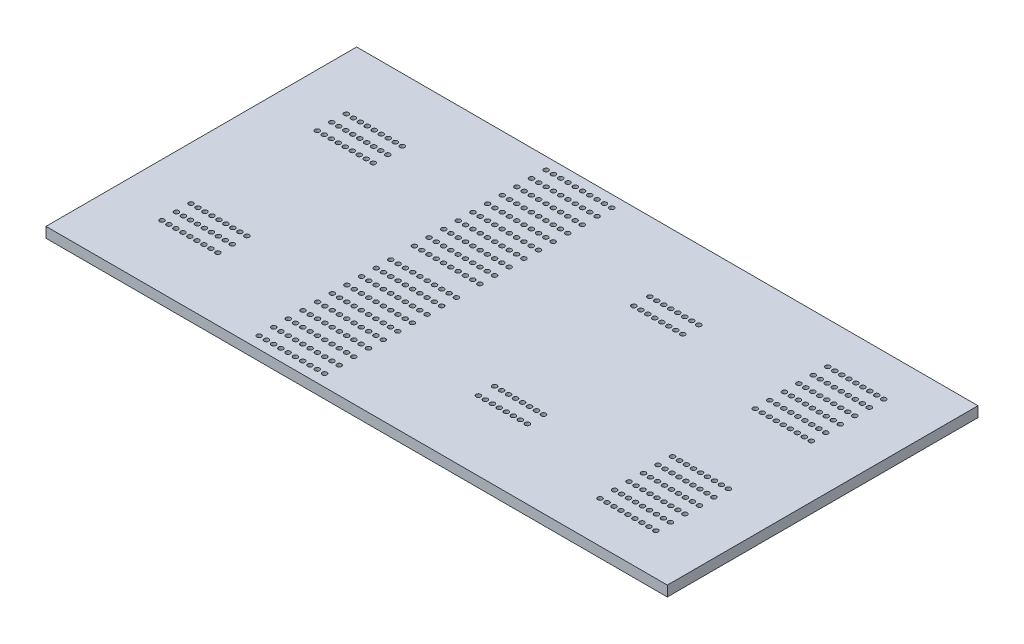
SolidWorks part; units mm, degrees
ref_plane "Plan de face" through (0, 0, 0) normal (0, 0, 1) x (1, 0, 0)
ref_plane "Plan de dessus" through (0, 0, 0) normal (0, 1, 0) x (1, 0, 0)
ref_plane "Plan de droite" through (0, 0, 0) normal (1, 0, 0) x (0, 0, -1)
sketch "Esquisse2" plane through (0, 0, 0) normal (0, 1, 0) x (1, 0, 0)
  line L1 (-60, -15) -> (60, -15)
  line L2 (-60, -15) -> (-60, 15)
  line L3 (-60, 15) -> (60, 15)
  line L4 (60, -15) -> (60, 15)
  line L5 (-60, -15) -> (60, 15) construction
  line L6 (-60, 15) -> (60, -15) construction
  point P0 (0, 0)
  dimension "D1" = 30
  dimension "D2" = 120
extrude "Boss.-Extru.1" add sketch "Esquisse2" along normal blind 2 contours L3 L4 L1 L2
sketch "Cavités" plane through (0, 0, 0) normal (0, 1, 0) x (1, 0, 0)
  line L0 (-60, -15) -> (60, -15) construction
  line L1 (-58.4, 15) -> (-30.4, 15) construction
  line L2 (-58.4, 15) -> (-58.4, -15) construction
  line L3 (-58.4, -15) -> (-30.4, -15) construction
  line L4 (-30.4, 15) -> (-30.4, -15) construction
  line L5 (-60, 15) -> (60, 15) construction
  line L6 (-28.8, 15) -> (-0.8, 15) construction
  line L7 (-28.8, 15) -> (-28.8, -15) construction
  line L8 (-28.8, -15) -> (-0.8, -15) construction
  line L9 (-0.8, 15) -> (-0.8, -15) construction
  line L10 (-30.4, 15) -> (-28.8, 15) construction
  line L11 (0.8, 15) -> (28.8, 15) construction
  line L12 (0.8, 15) -> (0.8, -15) construction
  line L13 (0.8, -15) -> (28.8, -15) construction
  line L14 (28.8, 15) -> (28.8, -15) construction
  line L15 (30.4, 15) -> (58.4, 15) construction
  line L16 (30.4, 15) -> (30.4, -15) construction
  line L17 (30.4, -15) -> (58.4, -15) construction
  line L18 (58.4, 15) -> (58.4, -15) construction
  line L19 (-0.8, 15) -> (0.8, 15) construction
  line L20 (28.8, 15) -> (30.4, 15) construction
  line L21 (-60, 15) -> (-58.4, 15) construction
  line L22 (58.4, 15) -> (60, 15) construction
  dimension "D1" = 28
  dimension "D2" = 1.6
sketch "Esquisse7" plane through (0, 2, 0) normal (0, 1, 0) x (1, 0, 0)
  line L0 (-58.4, 0) -> (-49.8, 0) construction
  line L1 (-49.8, 2.8) -> (-39, 2.8) construction
  line L2 (-49.8, 2.8) -> (-49.8, -2.8) construction
  line L3 (-49.8, -2.8) -> (-39, -2.8) construction
  line L4 (-39, 2.8) -> (-39, -2.8) construction
  line L5 (-58.4, 15) -> (-58.4, -15) construction
  line L6 (-39, 0) -> (-30.4, 0) construction
  line L7 (-30.4, 15) -> (-30.4, -15) construction
  dimension "D1" = 10.8
  dimension "D2" = 5.6
sketch "Esquisse8" plane through (0, 2, 0) normal (0, 1, 0) x (1, 0, 0)
  circle A0 centre (-49.8, 2.8) radius 0.45
  dimension "D1" = 0.9
extrude "Enlèv. mat.-Extru.3" cut sketch "Esquisse8" against normal up to next
pattern_linear "Répétition linéaire4" count 9 spacing 1.35 along (1, 0, 0) count 3 spacing 2.8 along (0, 0, 1) of "Enlèv. mat.-Extru.3"
sketch "Esquisse9" plane through (0, 2, 0) normal (0, 1, 0) x (1, 0, 0)
  line L0 (-28.8, 0) -> (-21.127, 0) construction
  line L1 (-21.127, 12.725) -> (-8.473, 12.725) construction
  line L2 (-21.127, 12.725) -> (-21.127, -12.725) construction
  line L3 (-21.127, -12.725) -> (-8.473, -12.725) construction
  line L4 (-8.473, 12.725) -> (-8.473, -12.725) construction
  line L5 (-28.8, 15) -> (-28.8, -15) construction
  line L6 (-8.473, 0) -> (-0.8, 0) construction
  line L7 (-0.8, 15) -> (-0.8, -15) construction
  dimension "D1" = 12.654
  dimension "D2" = 25.45
sketch "Esquisse10" plane through (0, 2, 0) normal (0, 1, 0) x (1, 0, 0)
  circle A0 centre (-21.127, 12.725) radius 0.45
  dimension "D1" = 0.9
extrude "Enlèv. mat.-Extru.4" cut sketch "Esquisse10" against normal up to next
pattern_linear "Répétition linéaire5" count 10 spacing 1.406 along (1, 0, 0) count 10 spacing 2.8278 along (0, 0, 1) of "Enlèv. mat.-Extru.4"
sketch "Esquisse11" plane through (0, 2, 0) normal (0, 1, 0) x (1, 0, 0)
  line L0 (0.8, 0) -> (10.075, 0) construction
  line L1 (10.075, 1.5555) -> (19.525, 1.5555) construction
  line L2 (10.075, 1.5555) -> (10.075, -1.5555) construction
  line L3 (10.075, -1.5555) -> (19.525, -1.5555) construction
  line L4 (19.525, 1.5555) -> (19.525, -1.5555) construction
  line L5 (0.8, 15) -> (0.8, -15) construction
  line L6 (19.525, 0) -> (28.8, 0) construction
  line L7 (28.8, 15) -> (28.8, -15) construction
  dimension "D1" = 9.45
  dimension "D2" = 3.111
sketch "Esquisse12" plane through (0, 2, 0) normal (0, 1, 0) x (1, 0, 0)
  circle A0 centre (10.075, 1.5555) radius 0.45
  dimension "D1" = 0.9
extrude "Enlèv. mat.-Extru.5" cut sketch "Esquisse12" against normal up to next
pattern_linear "Répétition linéaire6" count 8 spacing 1.35 along (1, 0, 0) count 2 spacing 3.111 along (0, 0, 1) of "Enlèv. mat.-Extru.5"
sketch "Esquisse13" plane through (0, 2, 0) normal (0, 1, 0) x (1, 0, 0)
  line L0 (30.4, 0) -> (39, 0) construction
  line L1 (39, 7) -> (49.8, 7) construction
  line L2 (39, 7) -> (39, -7) construction
  line L3 (39, -7) -> (49.8, -7) construction
  line L4 (49.8, 7) -> (49.8, -7) construction
  line L5 (30.4, 15) -> (30.4, -15) construction
  line L6 (49.8, 0) -> (58.4, 0) construction
  line L7 (58.4, 15) -> (58.4, -15) construction
  dimension "D1" = 14
  dimension "D2" = 10.8
sketch "Esquisse14" plane through (0, 2, 0) normal (0, 1, 0) x (1, 0, 0)
  circle A0 centre (39, 7) radius 0.45
  dimension "D1" = 0.9
extrude "Enlèv. mat.-Extru.6" cut sketch "Esquisse14" against normal up to next
pattern_linear "Répétition linéaire7" count 9 spacing 1.35 along (1, 0, 0) count 6 spacing 2.8 along (0, 0, 1) of "Enlèv. mat.-Extru.6"
mirror "Symétrie1" about plane through (-60, 2, 15) normal (0, 0, -1) of bodies 114
